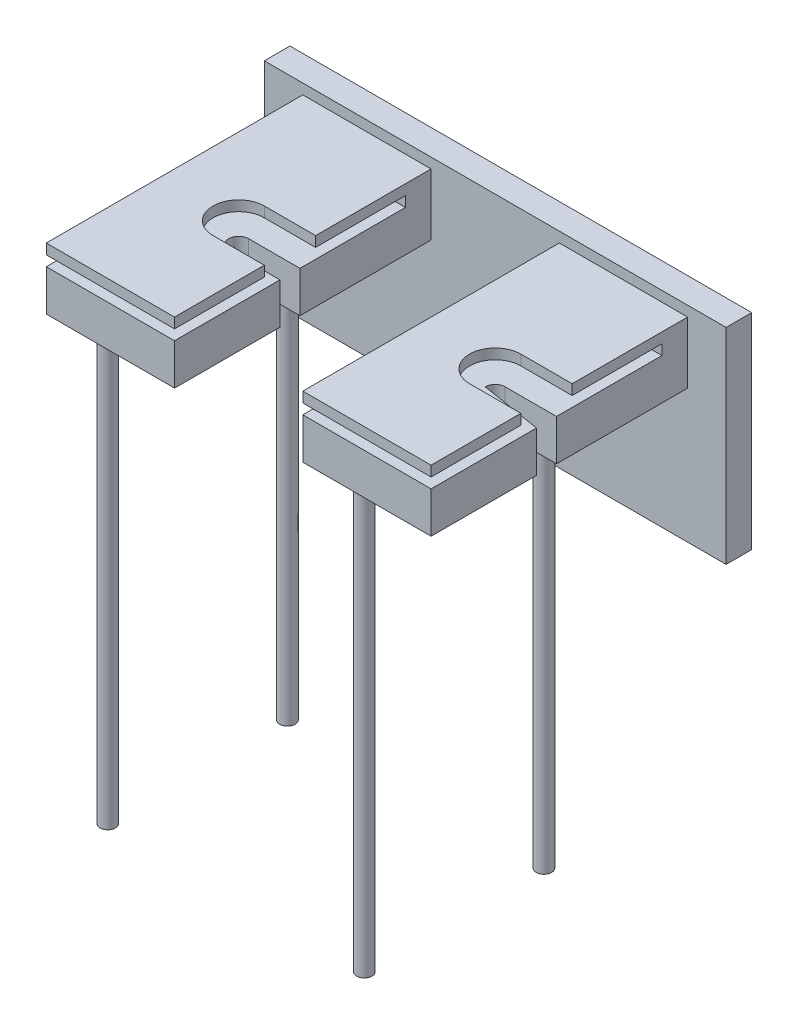
SolidWorks part; units mm, degrees
note: The reader was unsure of these and kept them because the rebuilt part matched: shared geometry of "Sketch10<3>", "Sketch11<5>".
other "syringeHolderLeft"
other "leftRail1"
other "syringeHolderRight"
other "holderBacking"
other "leftRail2"
other "rightRail1"
other "rightRail2" parameters "D1"=16.033, "D2"=35, "D3"=50, "D4"=200, "D5"=8.0186
ref_plane "Front Plane" through (0, 0, 0) normal (0, 0, 1) x (1, 0, 0)
ref_plane "Top Plane" through (0, 0, 0) normal (0, 1, 0) x (1, 0, 0)
ref_plane "Right Plane" through (0, 0, 0) normal (1, 0, 0) x (0, 0, -1)
sketch "Sketch1" plane through (0, 0, 0) normal (0, 0, 1) x (1, 0, 0)
  line L1 (-63.2842, 8.1459) -> (-38.2842, 8.1459)
  line L2 (-63.2842, 8.1459) -> (-63.2842, -3.8541)
  line L3 (-63.2842, -3.8541) -> (-38.2842, -3.8541)
  line L4 (-38.2842, 8.1459) -> (-38.2842, -3.8541)
  dimension "D1" = 25
  dimension "D2" = 12
extrude "Boss-Extrude1" add sketch "Sketch1" along normal blind 50
sketch "Sketch2" plane through (0, 0, 50) normal (0, 0, 1) x (1, 0, 0)
  line L0 (-63.2842, 8.1459) -> (-63.2842, -3.8541) construction
  line L1 (-63.2842, 6.1459) -> (-38.2842, 6.1459)
  line L2 (-63.2842, 6.1459) -> (-63.2842, 4.1459)
  line L3 (-63.2842, 4.1459) -> (-38.2842, 4.1459)
  line L4 (-38.2842, 6.1459) -> (-38.2842, 4.1459)
  line L5 (-38.2842, -3.8541) -> (-38.2842, 8.1459) construction
  line L6 (-38.2842, 8.1459) -> (-63.2842, 8.1459) construction
  dimension "D1" = 2
  dimension "D2" = 2
extrude "Cut-Extrude1" cut sketch "Sketch2" against normal blind 45
sketch "Sketch4" plane through (0, -3.8541, 0) normal (0, -1, 0) x (1, 0, 0)
  line L0 (-63.2842, 50) -> (-38.2842, 50) construction
  line L1 (-50.7842, 50) -> (-50.7842, 0) construction
  line L2 (-63.2842, 0) -> (-38.2842, 0) construction
  circle A0 centre (-50.7842, 37) radius 1.4224
  dimension "D1" = 2.8448
  dimension "D2" = 13
extrude "Cut-Extrude2" cut sketch "Sketch4" against normal up to surface (8 mm away) up to face at (-50.7842, 4.1459, 27.5)
sketch "Sketch6" plane through (0, 6.1459, 0) normal (0, -1, 0) x (1, 0, 0)
  line L0 (-38.2842, 50) -> (-38.2842, 0) construction
  line L1 (-48.2842, 32.5) -> (-38.2842, 32.5)
  line L2 (-48.2842, 22.5) -> (-38.2842, 22.5)
  line L3 (-38.2842, 22.5) -> (-38.2842, 32.5)
  line L4 (-48.2842, 22.5) -> (-48.2842, 32.5)
  circle A0 centre (-48.2842, 27.5) radius 5
  line M4 (-38.2842, 5) -> (-38.2842, 50)
  dimension "D2" = 10
  dimension "D1" = 10
extrude "Cut-Extrude3" cut sketch "Sketch6" against normal up to surface (2 mm away) contours A0 L2 L1 M4 | L4 A0 | L4 A0
pattern_linear "LPattern1" count 2 spacing 50 along (1, 0, 0) of bodies 104
sketch "Sketch7" plane through (0, 0, 0) normal (0, 0, -1) x (-1, 0, 0)
  line L1 (-19.2158, -29.8541) -> (70.7842, -29.8541)
  line L2 (-19.2158, -29.8541) -> (-19.2158, 10.1459)
  line L3 (-19.2158, 10.1459) -> (70.7842, 10.1459)
  line L4 (70.7842, -29.8541) -> (70.7842, 10.1459)
  line L5 (-11.7158, -3.8541) -> (-11.7158, 8.1459) construction
  line L6 (63.2842, 8.1459) -> (63.2842, -3.8541) construction
  line L7 (-11.7158, 8.1459) -> (13.2842, 8.1459) construction
  point P8 (-11.7158, 2.1459)
  dimension "D1" = 7.5
  dimension "D2" = 7.5
  dimension "D3" = 40
  dimension "D4" = 2
extrude "Boss-Extrude2" add sketch "Sketch7" along normal blind 5 separate body
sketch "Sketch8" plane through (0, 0, 50) normal (0, 0, 1) x (1, 0, 0)
  line L0 (-63.2842, 4.1459) -> (-63.2842, -3.8541) construction
  line L1 (-38.2842, -3.8541) -> (-38.2842, 4.1459) construction
  circle A0 centre (-59.2842, 0) radius 1.4224
  circle A1 centre (-42.2842, 0) radius 1.4224
  dimension "D1" = 2.8448
  dimension "D2" = 2.8448
  dimension "D3" = 4
  dimension "D4" = 4
sketch "Sketch9" plane through (0, 0, 50) normal (0, 0, 1) x (1, 0, 0)
  line L0 (-13.2842, 4.1459) -> (-13.2842, -3.8541) construction
  line L1 (11.7158, -3.8541) -> (11.7158, 4.1459) construction
  circle A0 centre (-9.2842, 0) radius 1.4224
  circle A1 centre (7.7158, 0) radius 1.4224
  dimension "D1" = 2.8448
  dimension "D2" = 2.8448
  dimension "D3" = 4
  dimension "D4" = 4
extrude "Cut-Extrude4" cut sketch "Sketch8" along normal blind 10 from surface at -55 starting at face at (-25.7842, -9.8541, -5)
extrude "Cut-Extrude5" cut sketch "Sketch9" along normal blind 10 from surface at -55 starting at face at (-57.8618, 0, -5)
sketch "Sketch10" plane through (0, 8.1459, 0) normal (0, 1, 0) x (1, 0, 0)
  circle A0 centre (-56.2842, -10) radius 1.5
  circle A1 centre (-56.3028, -45) radius 1.5
  point P4 (-48.2842, -27.5)
  dimension "D3" = 3
  dimension "D4" = 3
  dimension "D1" = 17.5
  dimension "D2" = 17.5
  dimension "D5" = 8
extrude "Boss-Extrude3" add sketch "Sketch10" against normal blind 90 from offset 7 separate body contours A1 | A0 offset against normal yes
extrude "Cut-Extrude6" cut sketch "Sketch10<3>" against normal up to surface (5 mm away) from offset 7 up to face at (-50.7842, -3.8541, 35.5776) offset against normal yes
sketch "Sketch10<3>" plane through (0, 8.1459, 0) normal (0, 1, 0) x (1, 0, 0) same geometry as "Sketch10"
sketch "Sketch11" plane through (0, 8.1459, 0) normal (0, 1, 0) x (1, 0, 0)
  circle A0 centre (-6.2842, -10) radius 1.5
  circle A1 centre (-6.2842, -45) radius 1.5
  point P4 (1.7158, -27.5)
  point P7 (1.7158, -27.5)
  dimension "D3" = 3
  dimension "D4" = 3
  dimension "D1" = 17.5
  dimension "D2" = 17.5
  dimension "D5" = 8
extrude "Boss-Extrude4" add sketch "Sketch11" against normal blind 90 from offset 7 separate body contours A1 | A0 offset against normal yes
extrude "Cut-Extrude7" cut sketch "Sketch11<5>" against normal up to surface (5 mm away) from offset 7 up to face at (-0.7842, -3.8541, 35.5776) offset against normal yes
sketch "Sketch11<5>" plane through (0, 8.1459, 0) normal (0, 1, 0) x (1, 0, 0) same geometry as "Sketch11"
sketch "Sketch12" plane through (0, 8.1459, 0) normal (0, 1, 0) x (1, 0, 0)
  line L0 (-48.2842, -25.55) -> (-38.2842, -25.55)
  line L1 (-38.2842, -5) -> (-38.2842, -50) construction
  line L2 (-38.2842, -25.55) -> (-38.2842, -29.45)
  line L3 (-38.2842, -29.45) -> (-48.2842, -29.45)
  line L4 (-48.2842, -29.45) -> (-48.2842, -25.55)
  circle A0 centre (-48.2842, -27.5) radius 1.95
  dimension "D1" = 3.9
extrude "Cut-Extrude8" cut sketch "Sketch12" along normal up to surface (8 mm away) from surface contours A0 L3 L2 L0 | L4 A0 | L4 A0
sketch "Sketch13" plane through (0, 8.1459, 0) normal (0, 1, 0) x (1, 0, 0)
  line L0 (1.7158, -25.55) -> (11.7158, -25.55)
  line L1 (11.7158, -5) -> (11.7158, -50) construction
  line L2 (11.7158, -25.55) -> (11.7158, -29.45)
  line L3 (11.7158, -29.45) -> (-0.2342, -27.5007)
  line L4 (-0.2342, -27.5007) -> (1.7158, -25.55)
  circle A0 centre (1.7158, -27.5) radius 1.95
  dimension "D1" = 3.9
extrude "Cut-Extrude9" cut sketch "Sketch13" along normal up to surface (8 mm away) from surface contours A0 L3 L2 L0 | L3 A0 L4 | L4 A0
equation "\"syringeLipThickness\"= 2"
equation "\"syringeLipDepth\"=25"
equation "\"syringeLipLength\"= 25 * 2"
equation "\"holderLength\"= \"syringeLipDepth\" * 4"
equation "\"holderThickness\"= 5"
equation "\"syringeLipHeight\"= \"syringeLipThickness\" * 6"
equation "\"D1@Sketch1\"=\"syringeLipDepth\""
equation "\"D1@Boss-Extrude1\"=\"syringeLipLength\""
equation "\"D2@Sketch1\"=\"syringeLipHeight\""
equation "\"D1@Sketch2\"=\"syringeLipThickness\""
equation "\"D2@Sketch2\"=\"syringeLipThickness\""
equation "\"D1@Cut-Extrude1\"=\"syringeLipLength\"-5"
equation "\"screwDiam\"= 2.8448"
equation "\"screwDist\"= 10"
equation "\"D1@Sketch4\"=\"screwDiam\""
equation "\"syringeDiam\"= 10"
equation "\"D1@Sketch6\"=\"syringeLipDepth\"*0.4"
equation "\"D2@Sketch6\"=\"syringeDiam\""
equation "\"holderSpacing\"= \"syringeLipDepth\" * 2"
equation "\"D3@LPattern1\"=\"holderSpacing\""
equation "\"D1@Sketch7\"=\"syringeLipDepth\"*0.3"
equation "\"D2@Sketch7\"=\"syringeLipDepth\"*0.3"
equation "\"holderHeight\"= 40"
equation "\"D3@Sketch7\"=\"holderHeight\""
equation "\"D1@Boss-Extrude2\"=\"holderThickness\""
equation "\"D4@Sketch7\"=\"syringeLipThickness\""
equation "\"D1@Sketch8\"=\"screwDiam\""
equation "\"D2@Sketch8\"=\"screwDiam\""
equation "\"D3@Sketch8\"=\"screwDist\"*0.4"
equation "\"D4@Sketch8\"=\"screwDist\"*0.4"
equation "\"D1@Sketch9\"=\"screwDiam\""
equation "\"D2@Sketch9\"=\"screwDiam\""
equation "\"D3@Sketch9\"=\"screwDist\"*0.4"
equation "\"D4@Sketch9\"=\"screwDist\"*0.4"
equation "\"screwDepth\"=10"
equation "\"D1@Cut-Extrude4\"=\"screwDepth\""
equation "\"D1@Cut-Extrude5\"=\"screwDepth\""
equation "\"motorHoleDist\"= 35"
equation "\"motorTrackDiam\"= 3"
equation "\"motorCenterOffset\"= 8"
equation "\"D1@Sketch10\"=\"motorHoleDist\"/2"
equation "\"D2@Sketch10\"=\"motorHoleDist\"/2"
equation "\"D3@Sketch10\"=\"motorTrackDiam\""
equation "\"D4@Sketch10\"=\"motorTrackDiam\""
equation "\"D5@Sketch10\"=\"motorCenterOffset\""
equation "\"syringeLength\"= 90"
equation "\"D1@Boss-Extrude3\"=\"syringeLength\""
equation "\"D1@Boss-Extrude4\"=\"syringeLength\""
equation "\"D1@Sketch12\"=\"linearDriverDiam\"*1.5"
equation "\"linearDriverDiam\"=2.6"
equation "\"D1@Sketch13\"=\"linearDriverDiam\"*1.5"
